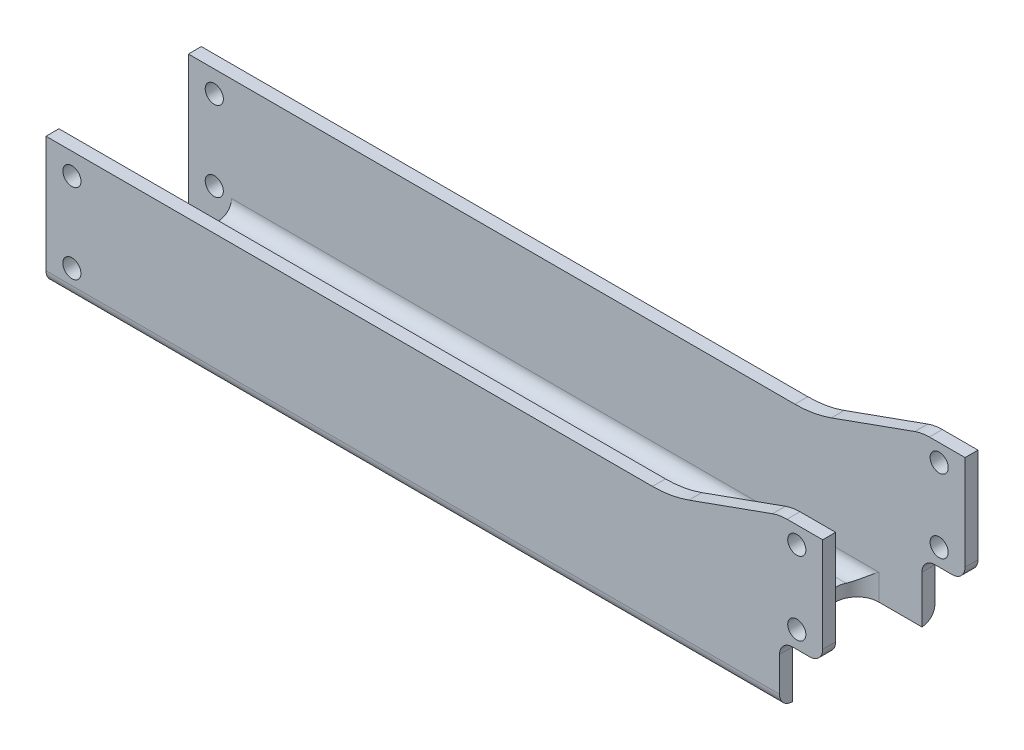
SolidWorks part; units mm, degrees
ref_plane "Front Plane" through (0, 0, 0) normal (0, 0, 1) x (1, 0, 0)
ref_plane "Top Plane" through (0, 0, 0) normal (0, 1, 0) x (1, 0, 0)
ref_plane "Right Plane" through (0, 0, 0) normal (1, 0, 0) x (0, 0, -1)
sketch "Sketch1" plane through (0, 0, 0) normal (0, 0, 1) x (1, 0, 0)
  line L0 (52.7874, 245.1803) -> (193.3525, 245.1803)
  line L4 (52.7874, 245.1803) -> (52.7874, 215.1803)
  line L5 (52.7874, 215.1803) -> (222.7874, 215.1803)
  line L6 (222.7874, 245.1803) -> (222.7874, 215.1803) construction
  line L7 (222.7874, 215.1803) -> (222.7874, 254.1811)
  line L8 (222.7874, 254.1811) -> (201.7956, 246.6492)
  line L9 (241.0832, 254.1811) -> (222.7874, 254.1811) construction
  arc A0 (201.7956, 246.6492) -> (193.3525, 245.1803) centre (193.3525, 270.1803) cw
extrude "Boss-Extrude1" add sketch "Sketch1" against normal blind 3
sketch "Sketch3" plane through (0, 0, -36) normal (0, 0, -1) x (-1, 0, 0)
  line L4 (-222.7874, 254.1811) -> (-222.7874, 215.1803)
  line L5 (-222.7874, 254.1811) -> (-222.7874, 215.1803)
  line L6 (-52.7874, 215.1803) -> (-52.7874, 245.1803)
  line L7 (-52.7874, 245.1803) -> (-193.3525, 245.1803)
  line L9 (-201.7956, 246.6492) -> (-222.7874, 254.1811)
  line L10 (-201.7956, 246.6492) -> (-222.7874, 254.1811)
  line L11 (-222.7874, 215.1803) -> (-52.7874, 215.1803)
  line L12 (-52.7874, 215.1803) -> (-52.7874, 245.1803)
  line L13 (-52.7874, 245.1803) -> (-193.3525, 245.1803)
  line L17 (-222.7874, 215.1803) -> (-52.7874, 215.1803)
  arc A1 (-201.7956, 246.6492) -> (-193.3525, 245.1803) centre (-193.3525, 270.1803) ccw
  arc A2 (-201.7956, 246.6492) -> (-193.3525, 245.1803) centre (-193.3525, 270.1803) ccw
  dimension "D1" = 0
extrude "Boss-Extrude2" add sketch "Sketch3" against normal blind 3 separate body
sketch "Sketch4" plane through (0, 0, -3) normal (0, 0, -1) x (-1, 0, 0)
  line L1 (-52.7874, 215.1803) -> (-207.7874, 215.1803)
  line L2 (-52.7874, 215.1803) -> (-52.7874, 218.1803)
  line L3 (-52.7874, 218.1803) -> (-207.7874, 218.1803)
  line L4 (-207.7874, 215.1803) -> (-207.7874, 218.1803)
extrude "Boss-Extrude3" add sketch "Sketch4" along normal up to surface (30 mm away) up to face at (157.7268, 236.8645, -33)
fillet "Fillet1" radius 5 2 edges at (207.7874, 216.6803, -33) (207.7874, 216.6803, -3)
ref_plane "Plane1" through (130.2874, 0, 0) normal (1, 0, 0) x (0, 0, -1)
fillet "Fillet2" radius 3 4 edges at (132.7874, 218.1803, -3) (132.7874, 218.1803, -33) (137.7874, 215.1803, 0) (137.7874, 215.1803, -36)
sketch "Sketch5" plane through (0, 218.1803, 0) normal (0, 1, 0) x (1, 0, 0)
  line L0 (52.7874, 33) -> (193.3525, 33) construction
  line L1 (52.7874, 3) -> (62.7874, 3)
  line L2 (52.7874, 3) -> (52.7874, 33)
  line L3 (52.7874, 33) -> (62.7874, 33)
  line L4 (62.7874, 3) -> (62.7874, 33)
extrude "Cut-Extrude1" cut sketch "Sketch5" against normal through all both and the other way through all
sketch "Sketch6" plane through (0, 0, 0) normal (0, 0, 1) x (1, 0, 0)
  line L4 (54.7876, 245.1805) -> (62.7877, 245.1806) construction
  line L5 (58.7876, 245.1805) -> (58.7876, 215.1803) construction
  line L6 (52.7874, 215.1803) -> (62.7874, 215.1803) construction
  circle A0 centre (58.7876, 240.1805) radius 2.1
  circle A1 centre (58.7876, 221.6803) radius 2.1
  point P1 (0, 0)
extrude "Cut-Extrude2" cut sketch "Sketch6" against normal up to surface (36 mm away) up to face at (157.7268, 237.8645, -36)
sketch "Sketch7" plane through (222.7874, 0, 0) normal (1, 0, 0) x (0, 0, -1)
  line L0 (0, 218.1803) -> (0, 254.1811) construction
  line L1 (3, 254.1811) -> (0, 254.1811)
  line L2 (3, 254.1811) -> (3, 229.1811)
  line L3 (3, 229.1811) -> (0, 229.1811)
  line L4 (0, 254.1811) -> (0, 229.1811)
  line L5 (36, 254.1811) -> (36, 218.1803) construction
  line L6 (33, 254.1811) -> (36, 254.1811)
  line L7 (33, 254.1811) -> (33, 229.1811)
  line L8 (33, 229.1811) -> (36, 229.1811)
  line L9 (36, 254.1811) -> (36, 229.1811)
extrude "Boss-Extrude4" add sketch "Sketch7" along normal blind 10
fillet "Fillet3" radius 3 4 edges at (222.7874, 229.1811, -34.5) (222.7874, 229.1811, -1.5) (232.7874, 229.1811, -34.5) (232.7874, 229.1811, -1.5)
sketch "Sketch9" plane through (0, 0, 0) normal (0, 0, 1) x (1, 0, 0)
  line L4 (222.7874, 254.1811) -> (230.7874, 254.1811) construction
  line L5 (226.7874, 254.1811) -> (226.7874, 229.1811) construction
  circle A0 centre (226.7874, 250.1811) radius 2.1
  circle A1 centre (226.7874, 233.1811) radius 2.1
  point P1 (0, 0)
  point P7 (0, 0)
extrude "Cut-Extrude3" cut sketch "Sketch9" against normal up to surface (36 mm away) up to face at (58.7876, 242.2805, -36)
fillet "Fillet4" radius 10 2 edges at (222.7874, 254.1811, -34.5) (222.7874, 254.1811, -1.5)
